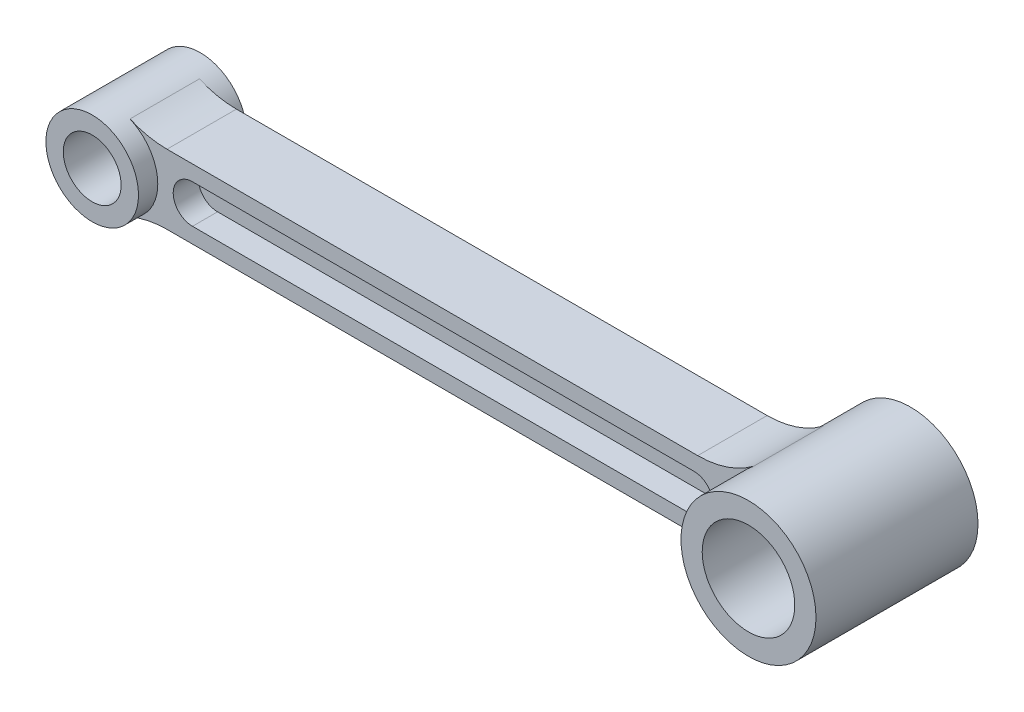
SolidWorks part; units mm, degrees
ref_plane "Front Plane" through (0, 0, 0) normal (0, 0, 1) x (1, 0, 0)
ref_plane "Top Plane" through (0, 0, 0) normal (0, 1, 0) x (1, 0, 0)
ref_plane "Right Plane" through (0, 0, 0) normal (1, 0, 0) x (0, 0, -1)
sketch "Sketch1" plane through (0, 0, 0) normal (0, 0, 1) x (1, 0, 0)
  line L0 (0, 0) -> (177.1372, 0) construction
  line L1 (7.9373, 9) -> (162.1289, 9)
  line L2 (7.9373, -9) -> (162.1289, -9)
  circle A0 centre (0, 0) radius 7.5
  circle A1 centre (0, 0) radius 12
  circle A5 centre (177.1372, 0) radius 12
  circle A6 centre (177.1372, 0) radius 17.5
  dimension "D1" = 15
  dimension "D2" = 24
  dimension "D3" = 24
  dimension "D4" = 35
  dimension "D5" = 9
extrude "Boss-Extrude1" add sketch "Sketch1" along normal mid plane 28 contours A0 A1 region at (10.6279, 4.7976, 0)
extrude "Boss-Extrude3" add sketch "Sketch1<5>" along normal mid plane 42 separate body contours A6 A5 region at (181.6744, 16.3886, 0)
sketch "Sketch1<5>" plane through (0, 0, 0) normal (0, 0, 1) x (1, 0, 0) same geometry as "Sketch1"
extrude "Boss-Extrude4" add sketch "Sketch1<6>" along normal mid plane 18 contours A1 L0 A6 L1 | L0 A1 L2 A6 region at (85.5951, 4.5317, 0) region at (85.5951, -4.5317, 0)
sketch "Sketch1<6>" plane through (0, 0, 0) normal (0, 0, 1) x (1, 0, 0) same geometry as "Sketch1"
sketch "Sketch2" plane through (0, 0, 0) normal (0, 0, 1) x (1, 0, 0)
  line L0 (21, 0) -> (151, 0) construction
  line L1 (21, 5) -> (151, 5)
  line L2 (21, -5) -> (151, -5)
  arc A0 (21, 5) -> (21, -5) centre (21, 0) ccw
  arc A1 (151, -5) -> (151, 5) centre (151, 0) ccw
  point P3 (86, 0)
  dimension "D1" = 5
  dimension "D2" = 130
  dimension "D3" = 86
extrude "Cut-Extrude3" cut sketch "Sketch2" along normal blind 6.5 from offset 2.5
mirror "Mirror1" about plane through (0, 0, 0) normal (0, 0, 1) of "Cut-Extrude3"
fillet "Fillet1" radius 24 4 edges at (7.9373, -9, 0) (162.1289, -9, 0) (162.1289, 9, 0) (7.9373, 9, 0)
